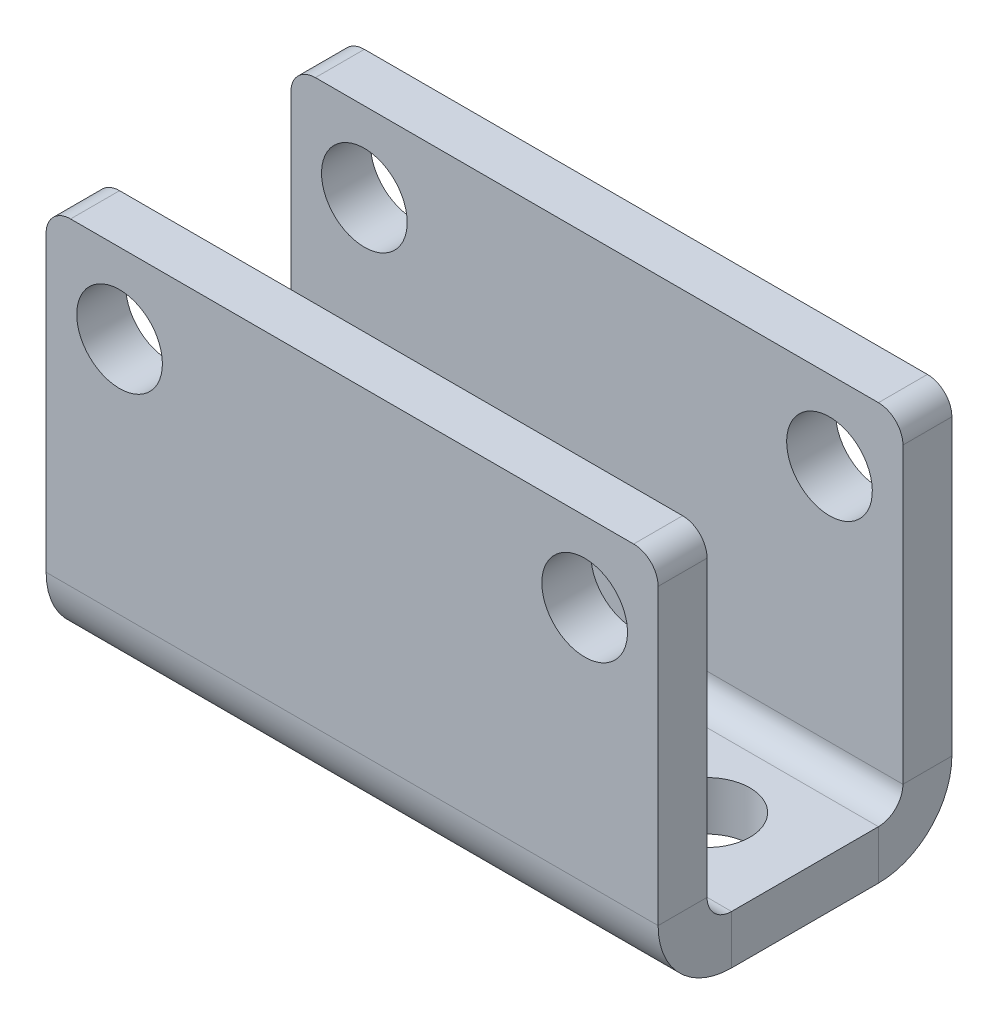
SolidWorks part; units mm, degrees
note: The reader was unsure of these and kept them because the rebuilt part matched: flange length of "Aresta-Flange2", "Aresta-Flange3".
ref_plane "Plano frontal" through (0, 0, 0) normal (0, 0, 1) x (1, 0, 0)
ref_plane "Plano superior" through (0, 0, 0) normal (0, 1, 0) x (1, 0, 0)
ref_plane "Plano direito" through (0, 0, 0) normal (1, 0, 0) x (0, 0, -1)
sketch "Esboço9" plane through (0, 0, 0) normal (0, 0, 1) x (1, 0, 0)
  line L1 (0, 0) -> (25, 0)
  line L2 (0, 0) -> (0, 16)
  line L3 (0, 16) -> (25, 16)
  line L4 (25, 0) -> (25, 16)
  dimension "D1" = 25
  dimension "D2" = 16
base flange "Flange-base2" sketch "Esboço9" thickness 2 reverse thickness direction yes parameters "D1"=0.7366
edge flange "Aresta-Flange2" sketch "Esboço17" flange angle 90 flange length 12 flange position material inside bend radius 1 thickness 2 relief rectangular parameters "D6"=10
sketch "Esboço17" plane through (0, 0, 0) normal (0, -1, 0) x (-1, 0, 0)
  line L2 (-25, 0) -> (-25, 10)
  line L3 (-25, 10) -> (0, 10)
  line L4 (0, 10) -> (0, 0)
  line L7 (0, 0) -> (-25, 0) construction
  line L8 (0, 0) -> (-25, 0)
bend "DobradeAresta2" bend radius 1 bend angle 90 parameters "D5"=1
edge flange "Aresta-Flange3" sketch "Esboço20" flange angle 90 flange length 16 flange position material inside bend radius 1 thickness 2 relief rectangular parameters "D6"=10
sketch "Esboço20" plane through (0, 2, -10) normal (0, 0, -1) x (-1, 0, 0)
  line L0 (0, 0) -> (-25, 0) construction
  line L1 (0, 0) -> (-25, 0)
  line L2 (-25, 0) -> (-25, 14)
  line L3 (-25, 14) -> (0, 14)
  line L4 (0, 14) -> (0, 0)
bend "DobradeAresta3" bend radius 1 bend angle 90 parameters "D5"=2
fillet "Filete1" radius 1 4 edges at (25, 16, -9) (0, 16, -9) (0, 16, 1) (25, 16, 1)
sketch "Esboço21" plane through (0, 0, 2) normal (0, 0, 1) x (1, 0, 0)
  line L0 (0, 12.75) -> (25, 12.75) construction
  line L1 (0, 15) -> (0, 3) construction
  line L2 (25, 3) -> (25, 15) construction
  line L3 (12.5, 16) -> (12.5, 3) construction
  line L4 (24, 16) -> (1, 16) construction
  line L5 (0, 3) -> (25, 3) construction
  circle A0 centre (3, 12.75) radius 1.75
  circle A1 centre (22, 12.75) radius 1.75
  dimension "D1" = 3
  dimension "D3" = 3.5
  dimension "D2" = 3.25
extrude "Corte-extrusão1" cut sketch "Esboço21" against normal up to surface (12 mm away) normal cut yes up to face at (12.5, 11.4024, -10)
sketch "Esboço22" plane through (0, 2, 0) normal (0, 1, 0) x (1, 0, 0)
  line L0 (0, 4) -> (25, 4) construction
  line L1 (0, 1) -> (0, 7) construction
  line L2 (25, 7) -> (25, 1) construction
  line L3 (12.5, 7) -> (12.5, 1) construction
  line L4 (0, 7) -> (25, 7) construction
  line L5 (25, 1) -> (0, 1) construction
  circle A0 centre (4, 4) radius 1.75
  circle A2 centre (21, 4) radius 1.75
  dimension "D1" = 3.5
  dimension "D2" = 4
  dimension "D3" = 17
extrude "Corte-extrusão2" cut sketch "Esboço22" against normal blind 10 normal cut yes
sketch "Curva-Linhas1" [suppressed] plane through (0, 0, 0) normal (0, 1, 0) x (1, 0, 0)
sketch "Caixa delimitadora1" [suppressed] plane through (0, 0, 0) normal (0, 1, 0) x (1, 0, 0)
sheet metal parameters "Chapa metálica2" thickness 2 parameters "D1"=0.7366
flat pattern "Padrão-Plano2" [suppressed]
sketch "Curva-Linhas3" plane through (0, 0, 0) normal (0, 1, 0) x (1, 0, 0)
sketch3d "Caixa delimitadora3" [suppressed]
  line L0 (0, 0, 0) -> (-25, 0, 0) construction
  line L1 (0, 10, 0) -> (-25, 10, 0) construction
  line L2 (0, 0, 0) -> (0, 10, 0) construction
  line L3 (-25, 0, 0) -> (-25, 10, 0) construction
sheet metal parameters "Chapa metálica3" thickness 2 parameters "D1"=0.7366
flat pattern "Padrão-Plano2"
sketch "Curva-Linhas3" plane through (0, 0, 0) normal (0, 0, -1) x (-1, 0, 0)
  line L0 (-25, 1.4292) -> (0, 1.4292) construction
  line L1 (-25, 1.4292) -> (0, 1.4292) construction
sketch3d "Caixa delimitadora3" [suppressed]
  line L0 (0, -7.1416, 0) -> (-25, -7.1416, 0) construction
  line L1 (0, 10, 0) -> (-25, 10, 0) construction
  line L2 (0, -7.1416, 0) -> (0, 10, 0) construction
  line L3 (-25, -7.1416, 0) -> (-25, 10, 0) construction
bend of the flat pattern "Planificar-<DobradeAresta2>1"
sheet metal parameters "Chapa metálica4" thickness 2 parameters "D1"=0.7366
flat pattern "Padrão-Plano2"
sketch "Curva-Linhas3" plane through (0, 0, 0) normal (0, 0, -1) x (-1, 0, 0)
  line L0 (-25, 1.4292) -> (0, 1.4292) construction
  line L1 (-25, 1.4292) -> (0, 1.4292) construction
  line L2 (-25, -10.7124) -> (0, -10.7124) construction
  line L3 (-25, -10.7124) -> (0, -10.7124) construction
sketch3d "Caixa delimitadora3" [suppressed]
  line L0 (-25, 10, 0) -> (-25, -19.2832, 0) construction
  line L1 (0, 10, 0) -> (0, -19.2832, 0) construction
  line L2 (-25, 10, 0) -> (0, 10, 0) construction
  line L3 (-25, -19.2832, 0) -> (0, -19.2832, 0) construction
bend of the flat pattern "Planificar-<DobradeAresta2>1"
bend of the flat pattern "Planificar-<DobradeAresta3>1"
sheet metal parameters "Chapa metálica5" thickness 2 parameters "D1"=0.7366
flat pattern "Padrão-Plano2"
sketch "Curva-Linhas3" plane through (0, 0, 0) normal (0, 0, -1) x (-1, 0, 0)
  line L0 (-25, 1.4292) -> (0, 1.4292) construction
  line L1 (-25, 1.4292) -> (0, 1.4292) construction
  line L2 (-25, -10.7124) -> (0, -10.7124) construction
  line L3 (-25, -10.7124) -> (0, -10.7124) construction
sketch3d "Caixa delimitadora3" [suppressed]
  line L0 (-25, 10, 0) -> (-25, -19.2832, 0) construction
  line L1 (0, 10, 0) -> (0, -19.2832, 0) construction
  line L2 (-25, 10, 0) -> (0, 10, 0) construction
  line L3 (-25, -19.2832, 0) -> (0, -19.2832, 0) construction
bend of the flat pattern "Planificar-<DobradeAresta2>1"
bend of the flat pattern "Planificar-<DobradeAresta3>1"
sheet metal parameters "Chapa metálica6" thickness 2 parameters "D1"=0.7366
flat pattern "Padrão-Plano2"
sketch "Curva-Linhas3" plane through (0, 0, 0) normal (0, 0, -1) x (-1, 0, 0)
  line L0 (-25, 1.4292) -> (0, 1.4292) construction
  line L1 (-25, 1.4292) -> (0, 1.4292) construction
  line L2 (-25, -7.7124) -> (0, -7.7124) construction
  line L3 (-25, -7.7124) -> (0, -7.7124) construction
sketch3d "Caixa delimitadora3" [suppressed]
  line L0 (-25, 16, 0) -> (-25, -22.2832, 0) construction
  line L1 (0, 16, 0) -> (0, -22.2832, 0) construction
  line L2 (-25, 16, 0) -> (0, 16, 0) construction
  line L3 (-25, -22.2832, 0) -> (0, -22.2832, 0) construction
bend of the flat pattern "Planificar-<DobradeAresta2>1"
bend of the flat pattern "Planificar-<DobradeAresta3>1"
